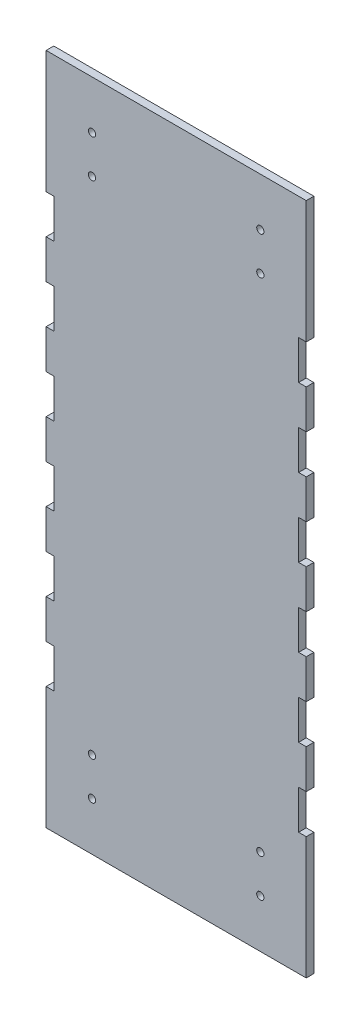
SolidWorks part; units mm, degrees
ref_plane "Front Plane" through (0, 0, 0) normal (0, 0, 1) x (1, 0, 0)
ref_plane "Top Plane" through (0, 0, 0) normal (0, 1, 0) x (1, 0, 0)
ref_plane "Right Plane" through (0, 0, 0) normal (1, 0, 0) x (0, 0, -1)
sketch "Sketch1" plane through (0, 0, 0) normal (0, 0, 1) x (1, 0, 0)
  line L5 (0, 279.4) -> (101.6, 279.4)
  line L87 (101.6, 0) -> (0, 0)
  line L88 (50.8, 279.4) -> (50.8, 0) construction
  line L89 (50.8, 139.7) -> (0, 139.7) construction
  line L90 (0, 0) -> (-3.175, 0)
  line L91 (-3.175, 0) -> (-3.175, 50.8)
  line L92 (-3.175, 50.8) -> (0, 50.8)
  line L93 (0, 50.8) -> (0, 0)
  line L94 (0, 228.6) -> (0, 279.4)
  line L95 (-3.175, 228.6) -> (0, 228.6)
  line L96 (-3.175, 279.4) -> (-3.175, 228.6)
  line L97 (0, 279.4) -> (-3.175, 279.4)
  line L98 (0, 50.8) -> (-3.175, 50.8)
  line L99 (-3.175, 50.8) -> (-3.175, 66.9636)
  line L100 (-3.175, 66.9636) -> (0, 66.9636)
  line L101 (0, 66.9636) -> (0, 50.8)
  line L102 (101.6, 228.6) -> (101.6, 279.4)
  line L103 (104.775, 228.6) -> (101.6, 228.6)
  line L104 (104.775, 279.4) -> (104.775, 228.6)
  line L105 (101.6, 279.4) -> (104.775, 279.4)
  line L106 (101.6, 66.9636) -> (101.6, 50.8)
  line L107 (104.775, 66.9636) -> (101.6, 66.9636)
  line L108 (104.775, 50.8) -> (104.775, 66.9636)
  line L109 (104.775, 50.8) -> (101.6, 50.8)
  line L110 (101.6, 50.8) -> (101.6, 0)
  line L111 (104.775, 0) -> (104.775, 50.8)
  line L112 (101.6, 0) -> (104.775, 0)
  line L113 (-3.175, 66.9636) -> (-3.175, 83.1273)
  line L114 (-3.175, 66.9636) -> (0, 66.9636)
  line L115 (0, 83.1273) -> (0, 66.9636)
  line L116 (-3.175, 83.1273) -> (0, 83.1273)
  line L117 (-3.175, 83.1273) -> (-3.175, 99.2909)
  line L118 (-3.175, 83.1273) -> (0, 83.1273)
  line L119 (0, 99.2909) -> (0, 83.1273)
  line L120 (-3.175, 99.2909) -> (0, 99.2909)
  line L121 (-3.175, 99.2909) -> (-3.175, 115.4545)
  line L122 (-3.175, 99.2909) -> (0, 99.2909)
  line L123 (0, 115.4545) -> (0, 99.2909)
  line L124 (-3.175, 115.4545) -> (0, 115.4545)
  line L125 (-3.175, 115.4545) -> (-3.175, 131.6182)
  line L126 (-3.175, 115.4545) -> (0, 115.4545)
  line L127 (0, 131.6182) -> (0, 115.4545)
  line L128 (-3.175, 131.6182) -> (0, 131.6182)
  line L129 (-3.175, 131.6182) -> (-3.175, 147.7818)
  line L130 (-3.175, 131.6182) -> (0, 131.6182)
  line L131 (0, 147.7818) -> (0, 131.6182)
  line L132 (-3.175, 147.7818) -> (0, 147.7818)
  line L133 (-3.175, 147.7818) -> (-3.175, 163.9455)
  line L134 (-3.175, 147.7818) -> (0, 147.7818)
  line L135 (0, 163.9455) -> (0, 147.7818)
  line L136 (-3.175, 163.9455) -> (0, 163.9455)
  line L137 (-3.175, 163.9455) -> (-3.175, 180.1091)
  line L138 (-3.175, 163.9455) -> (0, 163.9455)
  line L139 (0, 180.1091) -> (0, 163.9455)
  line L140 (-3.175, 180.1091) -> (0, 180.1091)
  line L141 (-3.175, 180.1091) -> (-3.175, 196.2727)
  line L142 (-3.175, 180.1091) -> (0, 180.1091)
  line L143 (0, 196.2727) -> (0, 180.1091)
  line L144 (-3.175, 196.2727) -> (0, 196.2727)
  line L145 (-3.175, 196.2727) -> (-3.175, 212.4364)
  line L146 (-3.175, 196.2727) -> (0, 196.2727)
  line L147 (0, 212.4364) -> (0, 196.2727)
  line L148 (-3.175, 212.4364) -> (0, 212.4364)
  line L149 (-3.175, 50.8) -> (-3.175, 66.9636) construction
  line L150 (0, 279.4) -> (0, 0)
  line L151 (104.775, 66.9636) -> (101.6, 66.9636)
  line L152 (101.6, 83.1273) -> (101.6, 66.9636)
  line L153 (104.775, 83.1273) -> (101.6, 83.1273)
  line L154 (104.775, 66.9636) -> (104.775, 83.1273)
  line L155 (104.775, 83.1273) -> (101.6, 83.1273)
  line L156 (101.6, 99.2909) -> (101.6, 83.1273)
  line L157 (104.775, 99.2909) -> (101.6, 99.2909)
  line L158 (104.775, 83.1273) -> (104.775, 99.2909)
  line L159 (104.775, 99.2909) -> (101.6, 99.2909)
  line L160 (101.6, 115.4545) -> (101.6, 99.2909)
  line L161 (104.775, 115.4545) -> (101.6, 115.4545)
  line L162 (104.775, 99.2909) -> (104.775, 115.4545)
  line L163 (104.775, 115.4545) -> (101.6, 115.4545)
  line L164 (101.6, 131.6182) -> (101.6, 115.4545)
  line L165 (104.775, 131.6182) -> (101.6, 131.6182)
  line L166 (104.775, 115.4545) -> (104.775, 131.6182)
  line L167 (104.775, 131.6182) -> (101.6, 131.6182)
  line L168 (101.6, 147.7818) -> (101.6, 131.6182)
  line L169 (104.775, 147.7818) -> (101.6, 147.7818)
  line L170 (104.775, 131.6182) -> (104.775, 147.7818)
  line L171 (104.775, 147.7818) -> (101.6, 147.7818)
  line L172 (101.6, 163.9455) -> (101.6, 147.7818)
  line L173 (104.775, 163.9455) -> (101.6, 163.9455)
  line L174 (104.775, 147.7818) -> (104.775, 163.9455)
  line L175 (104.775, 163.9455) -> (101.6, 163.9455)
  line L176 (101.6, 180.1091) -> (101.6, 163.9455)
  line L177 (104.775, 180.1091) -> (101.6, 180.1091)
  line L178 (104.775, 163.9455) -> (104.775, 180.1091)
  line L179 (104.775, 180.1091) -> (101.6, 180.1091)
  line L180 (101.6, 196.2727) -> (101.6, 180.1091)
  line L181 (104.775, 196.2727) -> (101.6, 196.2727)
  line L182 (104.775, 180.1091) -> (104.775, 196.2727)
  line L183 (104.775, 196.2727) -> (101.6, 196.2727)
  line L184 (101.6, 212.4364) -> (101.6, 196.2727)
  line L185 (104.775, 212.4364) -> (101.6, 212.4364)
  line L186 (104.775, 196.2727) -> (104.775, 212.4364)
  line L187 (104.775, 50.8) -> (104.775, 66.9636) construction
  line L188 (101.6, 279.4) -> (101.6, 50.8)
  line L189 (-3.175, 212.4364) -> (-3.175, 228.6)
  line L190 (-3.175, 212.4364) -> (0, 212.4364)
  line L191 (0, 228.6) -> (0, 212.4364)
  line L192 (-3.175, 228.6) -> (0, 228.6)
  line L193 (104.775, 212.4364) -> (101.6, 212.4364)
  line L194 (101.6, 228.6) -> (101.6, 212.4364)
  line L195 (104.775, 228.6) -> (101.6, 228.6)
  line L196 (104.775, 212.4364) -> (104.775, 228.6)
  dimension "D1" = 279.4
  dimension "D3" = 50.8
  dimension "D4" = 3.175
  dimension "D5" = 16.1636
  dimension "D7" = 16.1636
  dimension "D9" = 16.1636
  dimension "D2" = 101.6
  dimension "D6" = 11
  dimension "D8" = 11
extrude "Boss-Extrude1" add sketch "Sketch1" along normal blind 3.175 contours L188 L102 L5 L94 L150 L147 L143 L139 L135 L131 L127 L123 L119 L115 L101 L93 L87 L110 L106 L152 L156 L160 L164 L168 L172 L176 L180 L184 | L93 L92 L91 L90 | L116 L113 L100 L115 | L124 L121 L120 L123 | L132 L129 L128 L131 | L140 L137 L136 L139 | L148 L145 L144 L147 | L94 L97 L96 L95 | L105 L102 L103 L104 | L181 L186 L185 L184 | L173 L178 L177 L176 | L165 L170 L169 L168 | L157 L162 L161 L160 | L107 L154 L153 L152 | L110 L112 L111 L109
sketch "Sketch2" plane through (0, 0, 3.175) normal (0, 0, 1) x (1, 0, 0)
  line L0 (-3.175, 0) -> (-3.175, 50.8) construction
  line L1 (104.775, 0) -> (-3.175, 0) construction
  line L2 (50.8, 279.4) -> (50.8, 0) construction
  line L3 (-3.175, 279.4) -> (104.775, 279.4) construction
  line L4 (50.8, 139.7) -> (-3.175, 139.7) construction
  line L5 (-3.175, 131.6182) -> (-3.175, 147.7818) construction
  circle A0 centre (15.875, 20) radius 1.5
  circle A1 centre (15.875, 35.75) radius 1.5
  circle A2 centre (15.875, 243.65) radius 1.5
  circle A3 centre (15.875, 259.4) radius 1.5
  circle A4 centre (85.725, 259.4) radius 1.5
  circle A5 centre (85.725, 243.65) radius 1.5
  circle A6 centre (85.725, 35.75) radius 1.5
  circle A7 centre (85.725, 20) radius 1.5
  dimension "D1" = 3
  dimension "D2" = 3
  dimension "D3" = 15.75
  dimension "D4" = 19.05
  dimension "D5" = 20
extrude "Cut-Extrude1" cut sketch "Sketch2" against normal up to surface (3.175 mm away) up to face at (50.8, 139.7, 0)
equation "\"D7@Sketch1\"=\"D5@Sketch1\""
equation "\"D5@Sketch1\"=((\"D1@Sketch1\"-2*\"D3@Sketch1\")/(\"D6@Sketch1\"))"
equation "\"D8@Sketch1\"=\"D6@Sketch1\""
equation "\"D9@Sketch1\"=\"D5@Sketch1\""
